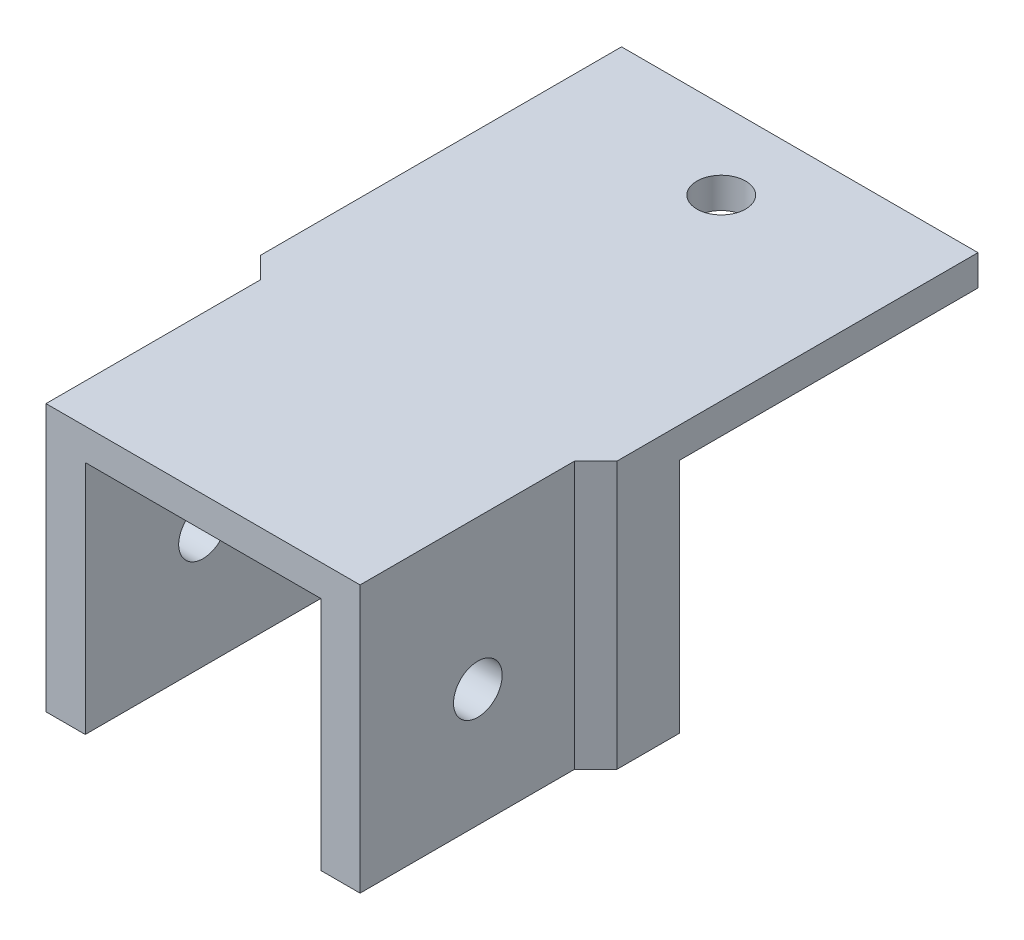
SolidWorks part; units mm, degrees
ref_plane "Front Plane" through (0, 0, 0) normal (0, 0, 1) x (1, 0, 0)
ref_plane "Top Plane" through (0, 0, 0) normal (0, 1, 0) x (1, 0, 0)
ref_plane "Right Plane" through (0, 0, 0) normal (1, 0, 0) x (0, 0, -1)
sketch "Sketch1" plane through (0, 0, 0) normal (0, 0, 1) x (1, 0, 0)
  line L0 (22.7, 15) -> (22.7, 19)
  line L1 (-22.7, -15) -> (22.7, -15)
  line L2 (-22.7, -15) -> (-22.7, 15)
  line L4 (22.7, -15) -> (22.7, 15)
  line L5 (-22.7, -15) -> (22.7, 15) construction
  line L6 (-22.7, 15) -> (22.7, -15) construction
  line L7 (-10, 10) -> (10, 10) construction
  line L8 (-10, 10) -> (-10, -10) construction
  line L9 (-10, -10) -> (10, -10) construction
  line L10 (10, 10) -> (10, -10) construction
  line L11 (-10, 10) -> (10, -10) construction
  line L12 (-10, -10) -> (10, 10) construction
  line L13 (22.7, 19) -> (-22.7, 19)
  line L14 (-22.7, 19) -> (-22.7, 15)
  circle A0 centre (-10, 10) radius 1.6
  circle A1 centre (10, 10) radius 1.6
  circle A2 centre (10, -10) radius 1.6
  circle A3 centre (-10, -10) radius 1.6
  point P0 (0, 0)
  point P6 (0, 0)
extrude "Boss-Extrude1" add sketch "Sketch1" along normal blind 5
sketch "Sketch3" plane through (0, 0, 5) normal (0, 0, 1) x (1, 0, 0)
  line L0 (22.7, -15) -> (22.7, 19)
  line L3 (-22.7, -15) -> (22.7, -15)
  line L5 (22.7, -15) -> (22.7, 19) construction
  line L6 (22.7, 19) -> (-22.7, 19)
  line L7 (-22.7, 19) -> (-22.7, -15)
  circle A0 centre (10, -10) radius 3
  circle A1 centre (10, 10) radius 3
  circle A2 centre (-10, 10) radius 3
  circle A3 centre (-10, -10) radius 3
extrude "Boss-Extrude2" add sketch "Sketch3" along normal blind 3
sketch "Sketch2" plane through (0, 0, 8) normal (0, 0, 1) x (1, 0, 0)
  line L0 (-22.7, -15) -> (22.7, -15) construction
  line L2 (15, -15) -> (22.7, -15)
  line L11 (-15, 15) -> (15, 15)
  line L13 (-15, 15) -> (-15, -15)
  line L15 (15, 15) -> (15, -15)
  line L16 (-15, 15) -> (15, -15) construction
  line L17 (-15, -15) -> (15, 15) construction
  line L20 (-22.7, -15) -> (-15, -15)
  line L21 (22.7, -15) -> (22.7, 19)
  line L22 (22.7, 19) -> (-22.7, 19)
  line L23 (-22.7, 19) -> (-22.7, -15)
  point P0 (0, 0)
  line M14 (-22.7, -15) -> (22.7, -15)
  line M46 (22.7, -15) -> (22.7, 19)
  line M47 (22.7, 19) -> (-22.7, 19)
  line M48 (-22.7, 19) -> (-22.7, -15)
extrude "Boss-Extrude3" add sketch "Sketch2" along normal blind 30 contours L11 L15 L13 M14 M46 M47 M48 region at (15.5672, 0, 8)
sketch "Sketch5" plane through (22.7, 0, 0) normal (1, 0, 0) x (0, 0, -1)
  line L0 (-38, -15) -> (-38, 0) construction
  line L2 (-38, -15) -> (-38, 19) construction
  line L3 (-38, 0) -> (-23, 0) construction
  circle A0 centre (-23, 0) radius 3.1
extrude "Cut-Extrude2" cut sketch "Sketch5" against normal through all
sketch "Sketch6" plane through (0, 19, 0) normal (0, 1, 0) x (1, 0, 0)
  line L0 (-22.7, 0) -> (-22.7, 38)
  line L1 (-22.7, 38) -> (22.7, 38)
  line L2 (22.7, 38) -> (22.7, 0)
  line L3 (22.7, 0) -> (-22.7, 0)
  line L4 (0, 0) -> (0, 28) construction
  circle A0 centre (0, 28) radius 3.1
extrude "Boss-Extrude4" add sketch "Sketch6" against normal blind 3.9
sketch "Sketch9" plane through (0, 0, 38) normal (0, 0, 1) x (1, 0, 0)
  line L0 (-22.7, -15) -> (-15, -15) construction
  line L1 (-22.7, 19) -> (-20, 19)
  line L2 (-22.7, 19) -> (-22.7, -15)
  line L3 (-22.7, -15) -> (-20, -15)
  line L4 (-20, 19) -> (-20, -15)
  line L7 (22.7, -15) -> (20, -15)
  line L8 (22.7, -15) -> (22.7, 19)
  line L9 (22.7, 19) -> (20, 19)
  line L10 (20, -15) -> (20, 19)
  line L11 (22.7, 19) -> (-22.7, 19) construction
extrude "Cut-Extrude3" cut sketch "Sketch9" against normal blind 30
chamfer "Chamfer1" distance 2.7 angle 45 2 edges at (20, 2, 8) (-20, 2, 8)
